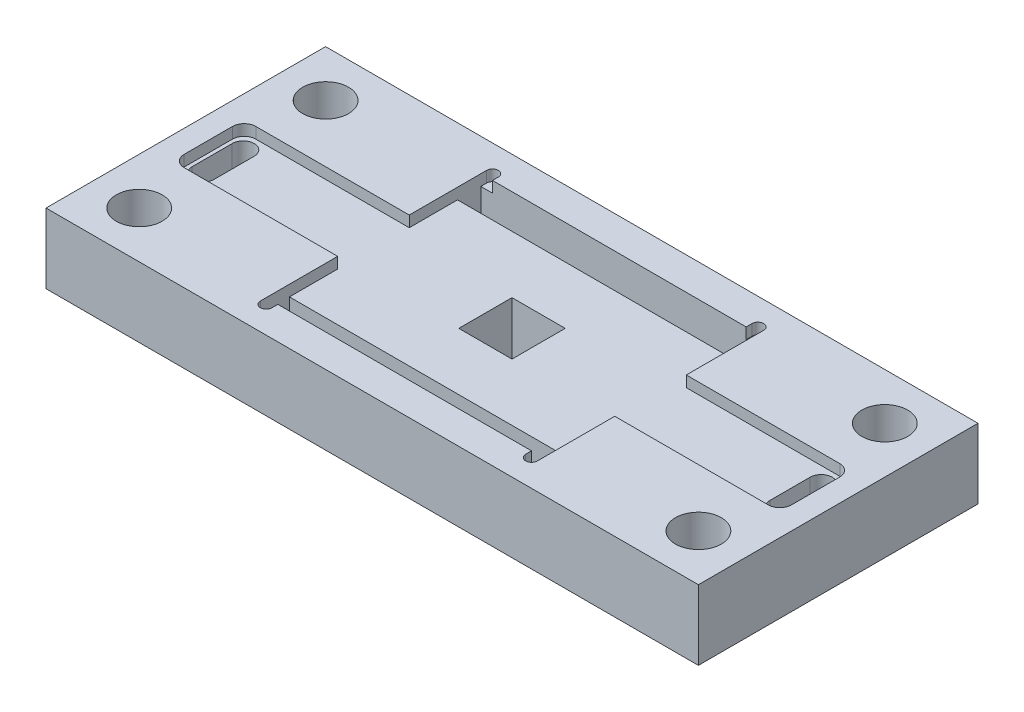
SolidWorks part; units mm, degrees
ref_plane "Front Plane" through (0, 0, 0) normal (0, 0, 1) x (1, 0, 0)
ref_plane "Top Plane" through (0, 0, 0) normal (0, 1, 0) x (1, 0, 0)
ref_plane "Right Plane" through (0, 0, 0) normal (1, 0, 0) x (0, 0, -1)
sketch "Sketch1" plane through (0, 0, 0) normal (0, 1, 0) x (1, 0, 0)
  line L1 (-88.9, -38.1) -> (88.9, -38.1)
  line L2 (-88.9, -38.1) -> (-88.9, 38.1)
  line L3 (-88.9, 38.1) -> (88.9, 38.1)
  line L4 (88.9, -38.1) -> (88.9, 38.1)
  line L5 (-88.9, -38.1) -> (88.9, 38.1) construction
  line L6 (-88.9, 38.1) -> (88.9, -38.1) construction
  point P0 (0, 0)
  dimension "D1" = 177.8
  dimension "D2" = 76.2
extrude "Boss-Extrude1" add sketch "Sketch1" against normal blind 19.05
sketch "Sketch2" plane through (0, 0, 0) normal (0, 1, 0) x (1, 0, 0)
  line L0 (37.75, 9.75) -> (82.75, 9.75)
  line L1 (-82.75, -9.75) -> (-37.75, -9.75)
  line L2 (-82.75, -9.75) -> (-82.75, 9.75)
  line L3 (-82.75, 9.75) -> (-37.75, 9.75)
  line L4 (82.75, -9.75) -> (82.75, 9.75)
  line L5 (-82.75, -9.75) -> (82.75, 9.75) construction
  line L6 (-82.75, 9.75) -> (82.75, -9.75) construction
  line L8 (-37.75, 9.75) -> (-37.75, 29.25)
  line L9 (-37.75, 29.25) -> (37.75, 29.25)
  line L10 (37.75, 9.75) -> (37.75, 29.25)
  line L11 (-37.75, 9.75) -> (37.75, 29.25) construction
  line L12 (-37.75, 29.25) -> (37.75, 9.75) construction
  line L13 (-37.75, -29.25) -> (37.75, -29.25)
  line L14 (-37.75, -29.25) -> (-37.75, -9.75)
  line L16 (37.75, -29.25) -> (37.75, -9.75)
  line L17 (-37.75, -29.25) -> (37.75, -9.75) construction
  line L18 (-37.75, -9.75) -> (37.75, -29.25) construction
  line L19 (37.75, -9.75) -> (82.75, -9.75)
  point P0 (0, 0)
  point P6 (0, 19.5)
  point P12 (0, -19.5)
  dimension "D1" = 19.5
  dimension "D2" = 165.5
  dimension "D3" = 75.5
  dimension "D4" = 19.5
extrude "Cut-Extrude1" cut sketch "Sketch2" against normal blind 3
sketch "Sketch3" plane through (0, -3, 0) normal (0, 1, 0) x (1, 0, 0)
  line L1 (-7.25, -7.25) -> (7.25, -7.25)
  line L2 (-7.25, -7.25) -> (-7.25, 7.25)
  line L3 (-7.25, 7.25) -> (7.25, 7.25)
  line L4 (7.25, -7.25) -> (7.25, 7.25)
  line L5 (-7.25, -7.25) -> (7.25, 7.25) construction
  line L6 (-7.25, 7.25) -> (7.25, -7.25) construction
  line L22 (37.75, 9.75) -> (37.75, 29.25) construction
  line L23 (-37.75, 29.25) -> (37.75, 29.25)
  line L24 (-37.75, 29.25) -> (-37.75, 22.9)
  line L25 (-37.75, 22.9) -> (37.75, 22.9)
  line L26 (37.75, 29.25) -> (37.75, 22.9)
  line L27 (37.75, -29.25) -> (37.75, -9.75) construction
  line L28 (-37.75, -29.25) -> (37.75, -29.25)
  line L29 (-37.75, -29.25) -> (-37.75, -22.9)
  line L30 (-37.75, -22.9) -> (37.75, -22.9)
  line L31 (37.75, -29.25) -> (37.75, -22.9)
  point P0 (0, 0)
  point P6 (-60, 0)
  point P11 (60, 0)
  dimension "D1" = 14.5
  dimension "D6" = 6.35
  dimension "D7" = 6.35
extrude "Cut-Extrude2" cut sketch "Sketch3" against normal through all
sketch "Sketch4" plane through (0, 0, 0) normal (0, 1, 0) x (1, 0, 0)
  line L0 (88.9, 38.1) -> (-88.9, 38.1) construction
  line L1 (-88.9, 38.1) -> (-88.9, -38.1) construction
  line L2 (-88.9, -38.1) -> (88.9, -38.1) construction
  line L3 (88.9, -38.1) -> (88.9, 38.1) construction
  circle A0 centre (-76.2, 25.4) radius 3.5
  circle A1 centre (76.2, 25.4) radius 3.5
  circle A2 centre (76.2, -25.4) radius 3.5
  circle A3 centre (-76.2, -25.4) radius 3.5
  dimension "D5" = 7
  dimension "D1" = 12.7
  dimension "D2" = 12.7
  dimension "D3" = 12.7
  dimension "D4" = 12.7
extrude "Cut-Extrude3" cut sketch "Sketch4" against normal through all
fillet "Fillet1" radius 3.175 4 edges at (-82.75, -1.5, 9.75) (-82.75, -1.5, -9.75) (82.75, -1.5, 9.75) (82.75, -1.5, -9.75)
sketch "Sketch5" plane through (0, 0, 0) normal (0, 1, 0) x (1, 0, 0)
  circle A0 centre (-76.2, -25.4) radius 6.25
  circle A1 centre (-76.2, 25.4) radius 6.25
  circle A2 centre (-76.2, -25.4) radius 3.5 construction
  circle A3 centre (76.2, 25.4) radius 6.25
  circle A4 centre (76.2, -25.4) radius 6.25
  dimension "D1" = 12.5
extrude "Cut-Extrude4" cut sketch "Sketch5" against normal blind 12.7
sketch "Sketch6" plane through (0, 0, 0) normal (0, 1, 0) x (1, 0, 0)
  line L1 (-37.75, 29.25) -> (-34.575, 29.25)
  line L2 (-37.75, 29.25) -> (-37.75, 32.43)
  line L3 (-37.75, 32.43) -> (-34.575, 32.43)
  line L4 (-34.575, 29.25) -> (-34.575, 32.43)
  line L5 (37.75, 29.25) -> (34.57, 29.25)
  line L6 (37.75, 29.25) -> (37.75, 32.43)
  line L7 (37.75, 32.43) -> (34.57, 32.43)
  line L8 (34.57, 29.25) -> (34.57, 32.43)
  line L9 (37.75, -29.25) -> (34.57, -29.25)
  line L10 (37.75, -29.25) -> (37.75, -32.43)
  line L11 (37.75, -32.43) -> (34.57, -32.43)
  line L12 (34.57, -29.25) -> (34.57, -32.43)
  line L13 (-37.75, -29.25) -> (-34.575, -29.25)
  line L14 (-37.75, -29.25) -> (-37.75, -32.43)
  line L15 (-37.75, -32.43) -> (-34.575, -32.43)
  line L16 (-34.575, -29.25) -> (-34.575, -32.43)
  dimension "D1" = 3.175
  dimension "D2" = 3.18
  dimension "D3" = 3.18
  dimension "D5" = 3.18
extrude "Cut-Extrude5" cut sketch "Sketch6" against normal blind 3
fillet "Fillet2" 2 edges at (-34.575, -1.5, -32.43) (-37.75, -1.5, -32.43) type full round first side face at (-34.575, -1.5, -30.84) second side face at (-37.75, -6.2625, -23.5825) middle face at (-36.1625, -1.5, -32.43)
fillet "Fillet3" 2 edges at (37.75, -1.5, -32.43) (34.57, -1.5, -32.43) type full round first side face at (37.75, -6.2625, -23.5825) second side face at (34.57, -1.5, -30.84) middle face at (36.16, -1.5, -32.43)
fillet "Fillet4" 2 edges at (-37.75, -1.5, 32.43) (-34.575, -1.5, 32.43) type full round first side face at (-37.75, -6.2625, 23.5825) second side face at (-34.575, -1.5, 30.84) middle face at (-36.1625, -1.5, 32.43)
fillet "Fillet5" 2 edges at (34.57, -1.5, 32.43) (37.75, -1.5, 32.43) type full round first side face at (34.57, -1.5, 30.84) second side face at (37.75, -6.2625, 23.5825) middle face at (36.16, -1.5, 32.43)
sketch "Sketch8" plane through (0, -3, 0) normal (0, 1, 0) x (1, 0, 0)
  line L0 (-78.75, 5.5) -> (-78.75, -5.5) construction
  line L1 (-75.75, 5.5) -> (-75.75, -5.5)
  line L2 (-81.75, 5.5) -> (-81.75, -5.5)
  line L3 (-82.75, 6.575) -> (-82.75, -6.575) construction
  arc A0 (-75.75, 5.5) -> (-81.75, 5.5) centre (-78.75, 5.5) ccw
  arc A1 (-81.75, -5.5) -> (-75.75, -5.5) centre (-78.75, -5.5) ccw
  point P2 (-78.75, 0)
  point P11 (-78.75, 8.5)
  point P12 (-78.75, -8.5)
  dimension "D1" = 1
  dimension "D2" = 6
  dimension "D3" = 17
extrude "Cut-Extrude6" cut sketch "Sketch8" against normal blind 35
sketch "Sketch9" plane through (0, -3, 0) normal (0, 1, 0) x (1, 0, 0)
  line L0 (78.75, 5.5) -> (78.75, -5.5) construction
  line L1 (81.75, 5.5) -> (81.75, -5.5)
  line L2 (75.75, 5.5) -> (75.75, -5.5)
  line L3 (82.75, -6.575) -> (82.75, 6.575) construction
  arc A0 (81.75, 5.5) -> (75.75, 5.5) centre (78.75, 5.5) ccw
  arc A1 (75.75, -5.5) -> (81.75, -5.5) centre (78.75, -5.5) ccw
  point P2 (78.75, 0)
  point P9 (78.75, 8.5)
  point P11 (78.75, -8.5)
  dimension "D1" = 1
  dimension "D2" = 6
  dimension "D3" = 17
extrude "Cut-Extrude7" cut sketch "Sketch9" against normal blind 35
